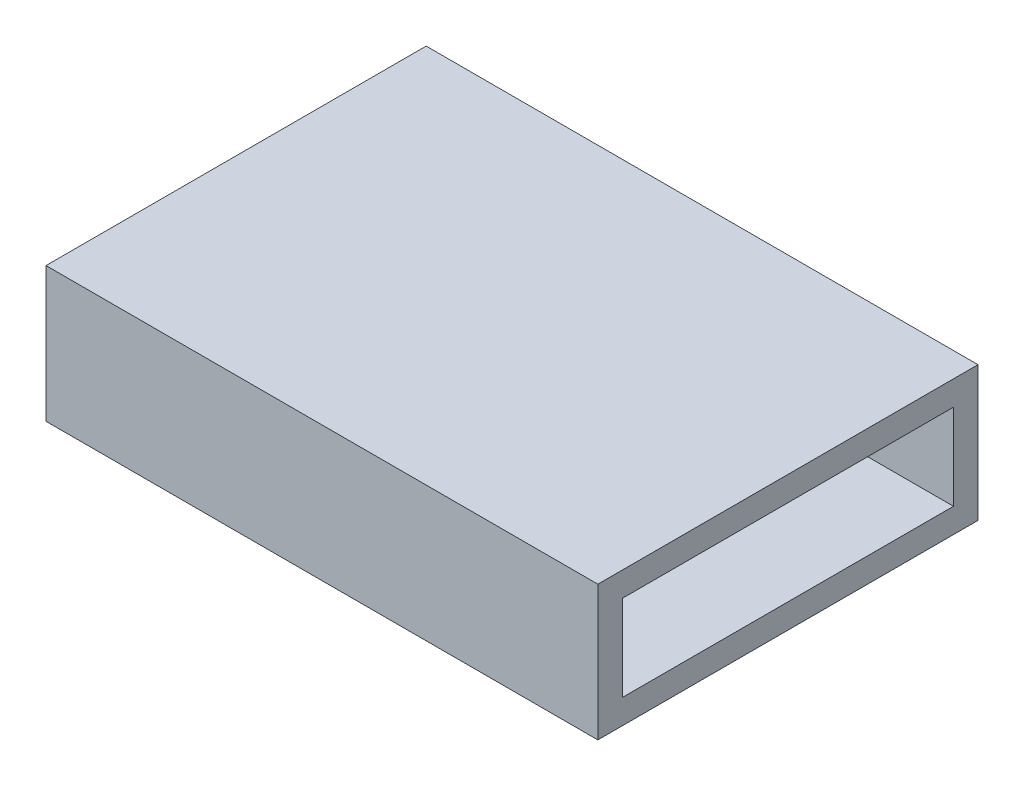
SolidWorks part; units mm, degrees
ref_plane "Front Plane" through (0, 0, 0) normal (0, 0, 1) x (1, 0, 0)
ref_plane "Top Plane" through (0, 0, 0) normal (0, 1, 0) x (1, 0, 0)
ref_plane "Right Plane" through (0, 0, 0) normal (1, 0, 0) x (0, 0, -1)
sketch "Sketch1" plane through (0, 0, 0) normal (1, 0, 0) x (0, 0, -1)
  line L0 (-6.2, -2.2) -> (-6.2, 2.2)
  line L1 (-5.4, -1.4) -> (5.4, -1.4)
  line L2 (-5.4, -1.4) -> (-5.4, 1.4)
  line L3 (-5.4, 1.4) -> (5.4, 1.4)
  line L4 (5.4, -1.4) -> (5.4, 1.4)
  line L5 (-5.4, -1.4) -> (5.4, 1.4) construction
  line L6 (-5.4, 1.4) -> (5.4, -1.4) construction
  line L7 (-6.2, 2.2) -> (6.2, 2.2)
  line L8 (6.2, -2.2) -> (6.2, 2.2)
  line L9 (-6.2, -2.2) -> (6.2, -2.2)
  line L10 (-4, 1.4) -> (-5.4, 0)
  line L11 (-5.4, 0) -> (-4, -1.4)
  line L12 (4, 1.4) -> (5.4, 0)
  line L13 (5.4, 0) -> (4, -1.4)
  arc A0 (-1.5, 1.4) -> (1.5, 1.4) centre (0, 3.4) ccw
  point P0 (0, 0)
  dimension "D6" = 5
  dimension "D1" = 0.8
  dimension "D2" = 10.8
  dimension "D3" = 2.8
  dimension "D4" = 90
  dimension "D5" = 90
  dimension "D7" = 2
extrude "Boss-Extrude1" add sketch "Sketch1" along normal blind 9 and the other way blind 9 contours L0 L9 L8 L7 L4 L1 L2 L3 region at (0, 0, 6.0684)
extrude "Boss-Extrude2" add sketch "Sketch1<3>" along normal blind 0.5 and the other way blind 0.5 contours L10 L3 L2 | L3 L12 L4 | L11 L2 L1 | L4 L13 L1 region at (0, -0.9333, 4.9333) region at (0, 0.9333, 4.9333) region at (0, -0.9333, -4.9333) region at (0, 0.9333, -4.9333)
sketch "Sketch1<3>" plane through (0, 0, 0) normal (1, 0, 0) x (0, 0, -1) same geometry as "Sketch1"
extrude "Boss-Extrude3" add sketch "Sketch1<4>" along normal blind 2 from offset 5 contours L3 A0 region at (0, 1.1982, 0)
sketch "Sketch1<4>" plane through (0, 0, 0) normal (1, 0, 0) x (0, 0, -1) same geometry as "Sketch1"
chamfer "Chamfer1" distance 2 angle 21 1 edges at (7, 0.9, 0) first distance on face at (6, 1.15, 0)
